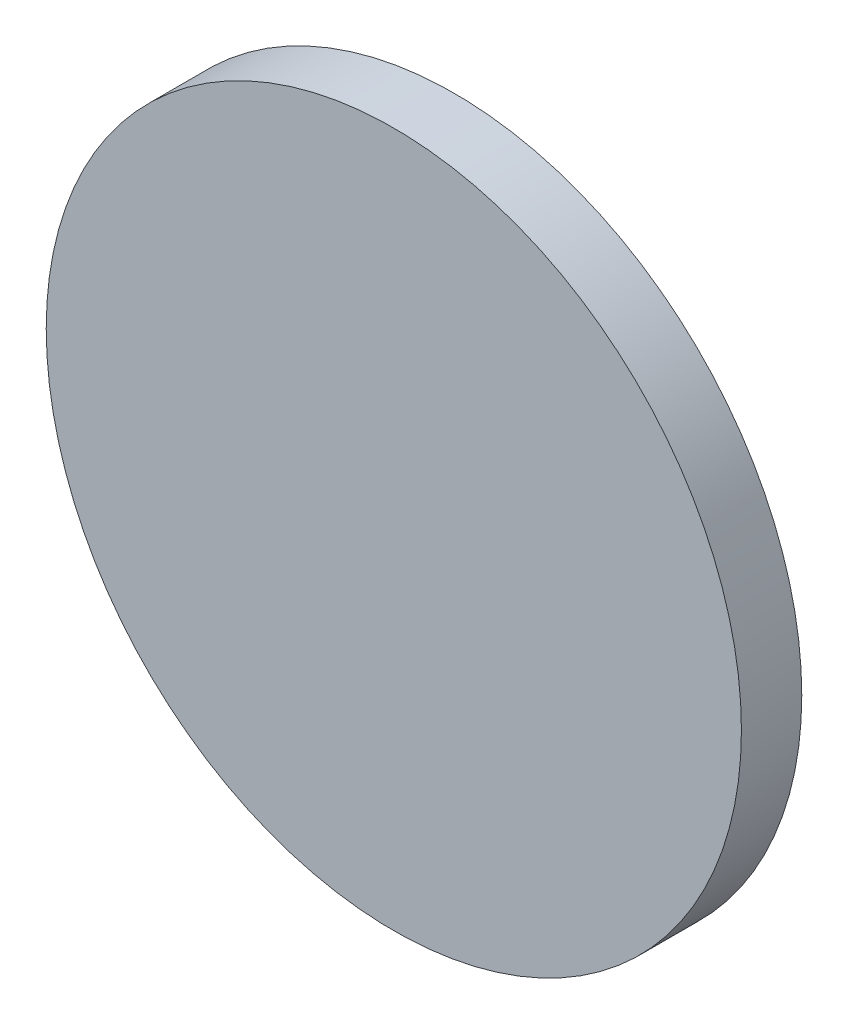
SolidWorks part; units mm, degrees
material "Nichel"
ref_plane "Piano frontale" through (0, 0, 0) normal (0, 0, 1) x (1, 0, 0)
ref_plane "Piano superiore" through (0, 0, 0) normal (0, 1, 0) x (1, 0, 0)
ref_plane "Piano destro" through (0, 0, 0) normal (1, 0, 0) x (0, 0, -1)
sketch "Schizzo1" plane through (0, 0, 0) normal (0, 0, 1) x (1, 0, 0)
  circle A0 centre (0, 0) radius 28.8
  dimension "D1" = 57.6
extrude "Estrusione-Estrusione1" add sketch "Schizzo1" along normal blind 5
